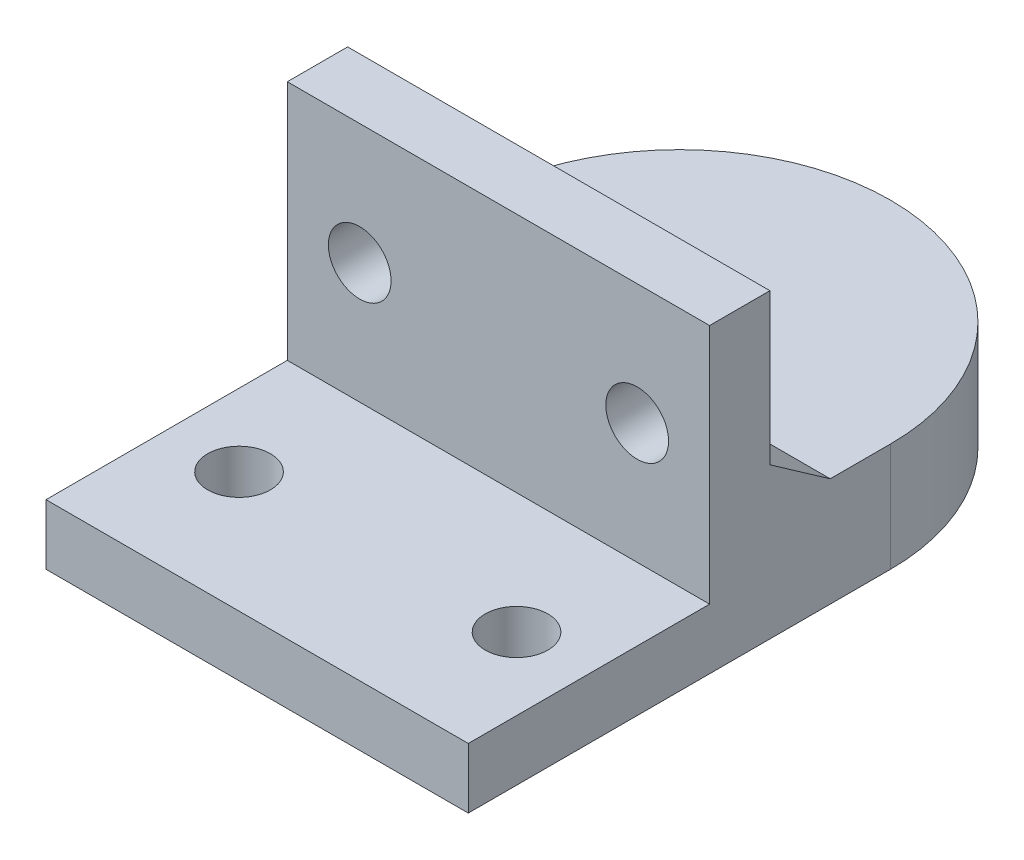
SolidWorks part; units mm, degrees
material "PET"
ref_plane "Front Plane" through (0, 0, 0) normal (0, 0, 1) x (1, 0, 0)
ref_plane "Top Plane" through (0, 0, 0) normal (0, 1, 0) x (1, 0, 0)
ref_plane "Right Plane" through (0, 0, 0) normal (1, 0, 0) x (0, 0, -1)
sketch "Sketch1" plane through (0, 0, 0) normal (0, 1, 0) x (1, 0, 0)
  line L5 (-17.5, 0) -> (-17.5, -15)
  line L6 (17.5, 0) -> (17.5, -15)
  line L9 (-17.5, -15) -> (17.5, -15)
  circle A0 centre (0, 0) radius 11.1
  arc A1 (17.5, 0) -> (-17.5, 0) centre (0, 0) ccw
  dimension "D1" = 22.2
  dimension "D2" = 35
  dimension "D3" = 15
extrude "Boss-Extrude1" add sketch "Sketch1" along normal blind 7
sketch "Sketch4" plane through (0, 0, 0) normal (0, 1, 0) x (1, 0, 0)
  line L0 (-17.5, -15) -> (17.5, -15) construction
  line L1 (-17.5, -15) -> (17.5, -15)
  line L2 (-17.5, -15) -> (-17.5, -35)
  line L3 (-17.5, -35) -> (17.5, -35)
  line L4 (17.5, -15) -> (17.5, -35)
  line L5 (-17.5, 0) -> (-17.5, -15) construction
  point P6 (0, -15)
  dimension "D1" = 20
extrude "Boss-Extrude3" add sketch "Sketch4" along normal blind 5
sketch "Sketch5" plane through (0, 7, 0) normal (0, 1, 0) x (1, 0, 0)
  line L0 (-17.5, -35) -> (17.5, -35) construction
  line L1 (-17.5, 0) -> (-17.5, -15) construction
  line L2 (17.5, -15) -> (17.5, 0) construction
  circle A0 centre (-11.5, -25) radius 2.6
  circle A1 centre (11.5, -25) radius 2.6
  dimension "D1" = 5.2
  dimension "D2" = 5.2
  dimension "D3" = 10
  dimension "D4" = 10
  dimension "D5" = 6
  dimension "D6" = 6
extrude "Cut-Extrude1" cut sketch "Sketch5" against normal through all
sketch "Sketch8" plane through (0, 7, 0) normal (0, 1, 0) x (1, 0, 0)
  line L0 (-17.5, -35) -> (17.5, -35) construction
  line L5 (-17.5, 0) -> (-17.5, -15)
  line L6 (17.5, 0) -> (17.5, -15)
  line L9 (-17.5, -15) -> (17.5, -15)
  arc A1 (17.5, 0) -> (-17.5, 0) centre (0, 0) ccw
  dimension "D1" = 20
  dimension "D2" = 35
extrude "Boss-Extrude4" add sketch "Sketch8" along normal blind 2
sketch "Sketch9" plane through (0, 9, 0) normal (0, 1, 0) x (1, 0, 0)
  line L0 (17.5, -15) -> (17.5, 0) construction
  line L1 (-17.5, -15) -> (17.5, -15)
  line L2 (-17.5, -15) -> (-17.5, -10)
  line L3 (-17.5, -10) -> (17.5, -10)
  line L4 (17.5, -15) -> (17.5, -10)
  dimension "D1" = 5
extrude "Boss-Extrude5" add sketch "Sketch9" along normal blind 16
sketch "Sketch10" plane through (0, 0, 15) normal (0, 0, 1) x (1, 0, 0)
  line L0 (-17.5, 15) -> (17.5, 15) construction
  line L1 (-17.5, 25) -> (-17.5, 5) construction
  line L2 (17.5, 25) -> (17.5, 5) construction
  line L3 (-17.5, 25) -> (17.5, 25) construction
  line L4 (-17.5, 7) -> (17.5, 7) construction
  circle A0 centre (-11.5, 15) radius 2.6
  circle A1 centre (11.5, 15) radius 2.6
  point P4 (0, 0)
  point P5 (-11.5953, 17)
  dimension "D1" = 5.2
  dimension "D2" = 5.2
  dimension "D3" = 6
  dimension "D4" = 6
  dimension "D5" = 10
  dimension "D6" = 8
extrude "Cut-Extrude2" cut sketch "Sketch10" against normal through all
chamfer "Chamfer2" distance 5 angle 35 1 edges at (0, 9, 10) first distance on face at (0, 9, 0.625)
sketch "Sketch11" plane through (0, 0, 10) normal (0, 0, -1) x (-1, 0, 0)
  circle A0 centre (-11.5, 15) radius 5
  circle A1 centre (11.5, 15) radius 5
  dimension "D1" = 10
  dimension "D2" = 10
extrude "Cut-Extrude3" cut sketch "Sketch11" along normal blind 18
equation "\"tolerance\"= 0.2"
equation "\"D1@Sketch1\"=\"tolerance\"+22"
equation "\"D1@Sketch5\"=\"tolerance\"+5"
equation "\"D2@Sketch5\"=\"tolerance\"+5"
equation "\"D1@Sketch10\"=\"tolerance\"+5"
equation "\"D2@Sketch10\"=\"tolerance\"+5"
